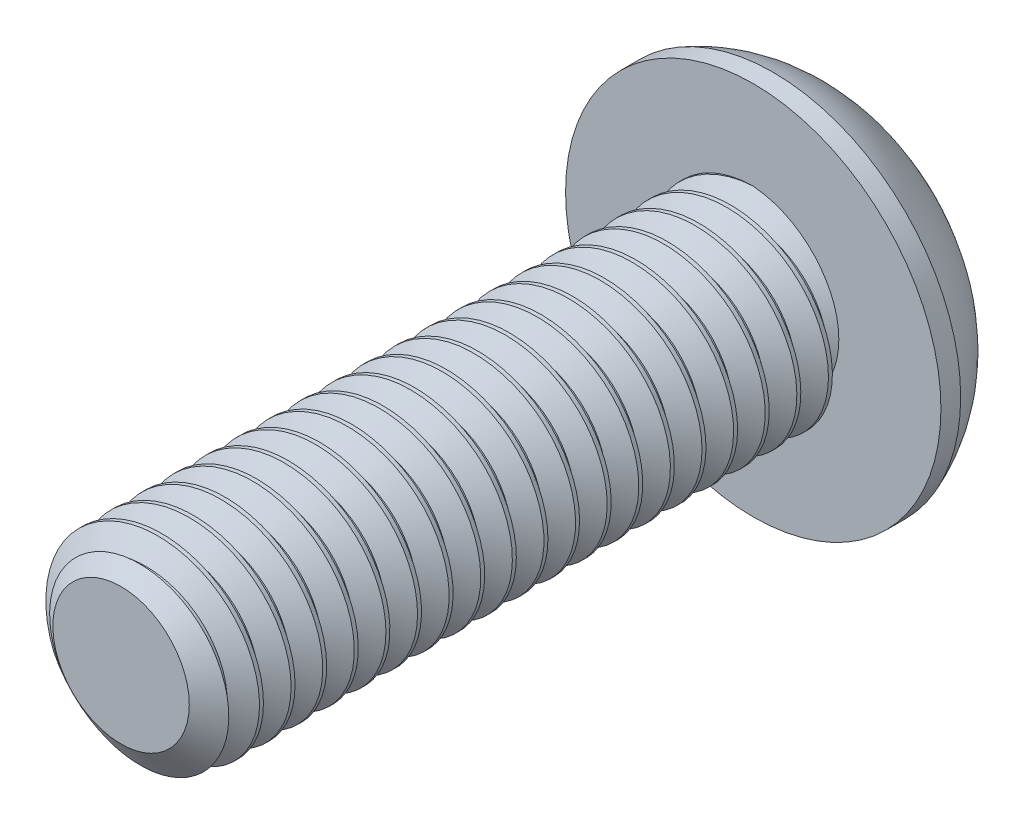
SolidWorks part; units mm, degrees
ref_plane "Front Plane" through (0, 0, 0) normal (0, 0, 1) x (1, 0, 0)
ref_plane "Top Plane" through (0, 0, 0) normal (0, 1, 0) x (1, 0, 0)
ref_plane "Right Plane" through (0, 0, 0) normal (1, 0, 0) x (0, 0, -1)
sketch "Sketch1" plane through (0, 0, 0) normal (0, 0, 1) x (1, 0, 0)
  circle A0 centre (0, 0) radius 2.5
  dimension "OD" = 5
extrude "Extrude1" add sketch "Sketch1" against normal blind 16
sketch "Sketch2" plane through (0, 0, 0) normal (0, 0, 1) x (1, 0, 0)
  circle A0 centre (0, 0) radius 2.5 construction
  circle A1 centre (0, 0) radius 2.5
curve "Helix/Spiral1" pitch 0.8 height 16.8 turns 21 parameters "pitch"=0.8
sketch "Sketch3" plane through (0, 0, 0) normal (1, 0, 0) x (0, 0, -1)
  line L0 (-0.7, 2.5) -> (-0.4, 1.9804)
  line L1 (-0.4, 1.9804) -> (-0.3, 1.9804)
  line L2 (-0.3, 1.9804) -> (0, 2.5)
  line L3 (-0.7, 2.5) -> (0, 2.5)
  line L4 (-0.35, 2.5) -> (-0.35, 1.9804) construction
  line L5 (-0.55, 2.2402) -> (-0.15, 2.2402) construction
  line L6 (0, 2.5) -> (0, -2.5) construction
  dimension "D1" = 0.1
  dimension "D2" = 0.4
  dimension "D3" = 60
sweep "Cut-Sweep1" cut profiles "Sketch3" path "Helix/Spiral1"
sketch "Sketch4" plane through (0, 0, 0) normal (1, 0, 0) x (0, 0, -1)
  line L0 (0.5417, 2.5) -> (0, 1.7264)
  line L1 (0, 1.7264) -> (0, 2.5)
  line L2 (0.5417, 2.5) -> (0, 2.5)
  line L3 (-0.7, 2.5) -> (0, 2.5) construction
  line L4 (0, 0) -> (7.0209, 0) construction
  dimension "D1" = 55
  dimension "D2" = 0.254
revolve "Cut-Revolve1" cut sketch "Sketch4" angle 360 about L4
sketch "Sketch5" plane through (0, 0, 0) normal (1, 0, 0) x (0, 0, -1)
  line L0 (16, -1.991) -> (16, 1.7838) construction
  line L1 (16, 2.627) -> (28.1202, 2.627)
  line L2 (16, 2.627) -> (16, 0)
  line L3 (16, 0) -> (28, 0)
  line L4 (28, 2.2968) -> (28, 0)
  line L5 (28.1202, 2.627) -> (28, 2.2968)
  line L6 (0, 0) -> (9.9695, 0) construction
  point P3 (28, 2.627)
  point P10 (28, 2.627)
  dimension "D1" = 0.3302
  dimension "Thread min" = 28
  dimension "D2" = 0.127
  dimension "D3" = 20
sketch "Sketch6" plane through (0, 0, -16) normal (0, 0, -1) x (-1, 0, 0)
  circle A0 centre (0, 0) radius 4.75
  dimension "head dia" = 9.5
extrude "Extrude2" add sketch "Sketch6" along normal blind 2.75
sketch "Sketch10" plane through (0, 0, 0) normal (1, 0, 0) x (0, 0, -1)
  line L0 (18.75, -4.75) -> (18.75, 4.75) construction
  line L1 (0, 0) -> (15.9584, 0) construction
  line L2 (18.75, 4.75) -> (16, 4.75) construction
  line L3 (16, 4.75) -> (16, -4.75) construction
  line L4 (16.5, 4.75) -> (16.5, 5.25)
  line L5 (16.5, 5.25) -> (19.25, 5.25)
  line L6 (19.25, 5.25) -> (19.25, 1.5)
  line L7 (18.75, 1.5) -> (19.25, 1.5)
  arc A0 (18.75, 1.5) -> (16.5, 4.75) centre (15.2778, 1.5) ccw
  dimension "D1" = 3
  dimension "D2" = 0.5
  dimension "D3" = 0.5
revolve "Cut-Revolve2" cut sketch "Sketch10" angle 360 about L1
ref_plane "Plane1" through (0, 0, -18.75) normal (0, 0, 1) x (1, 0, 0)
sketch "Sketch7" plane through (0, 0, -18.75) normal (0, 0, -1) x (-1, 0, 0)
  line L1 (0, 1.7321) -> (-1.5, 0.866)
  line L2 (-1.5, 0.866) -> (-1.5, -0.866)
  line L3 (-1.5, -0.866) -> (0, -1.7321)
  line L4 (0, -1.7321) -> (1.5, -0.866)
  line L5 (1.5, -0.866) -> (1.5, 0.866)
  line L6 (1.5, 0.866) -> (0, 1.7321)
  circle A0 centre (0, 0) radius 1.5 construction
  dimension "hex dia" = 3
extrude "Cut-Extrude1" cut sketch "Sketch7" against normal blind 2.25
sketch "Sketch8" plane through (0, 0, -18.75) normal (0, 0, 1) x (1, 0, 0)
  circle A0 centre (0, 0) radius 1.7321
extrude "Cut-Extrude2" cut sketch "Sketch8" along normal through all draft 45
sketch "Sketch9" plane through (0, 0, 0) normal (1, 0, 0) x (0, 0, -1)
  line L0 (0, 2.5) -> (0, -2.5) construction
  line L1 (4.4, 2.5) -> (4.4, -2.5) construction
  dimension "D1" = 4.4
equation "\"D3@Helix/Spiral1\" = \"screw length@Extrude1\"+\"pitch@Helix/Spiral1\""
equation "\"D1@Sketch3\" = \"pitch@Helix/Spiral1\"*.125"
equation "\"D2@Sketch3\" = \"pitch@Helix/Spiral1\"*.5"
equation "\"D1@Cut-Extrude1\" = \"hex dia@Sketch7\"*.75"
equation "\"D1@Sketch9\" = \"pitch@Helix/Spiral1\"*5.5"
equation "\"D1@Sketch10\" = \"hex dia@Sketch7\""
equation "\"D1@Plane1\" = \"head depth@Extrude2\""
